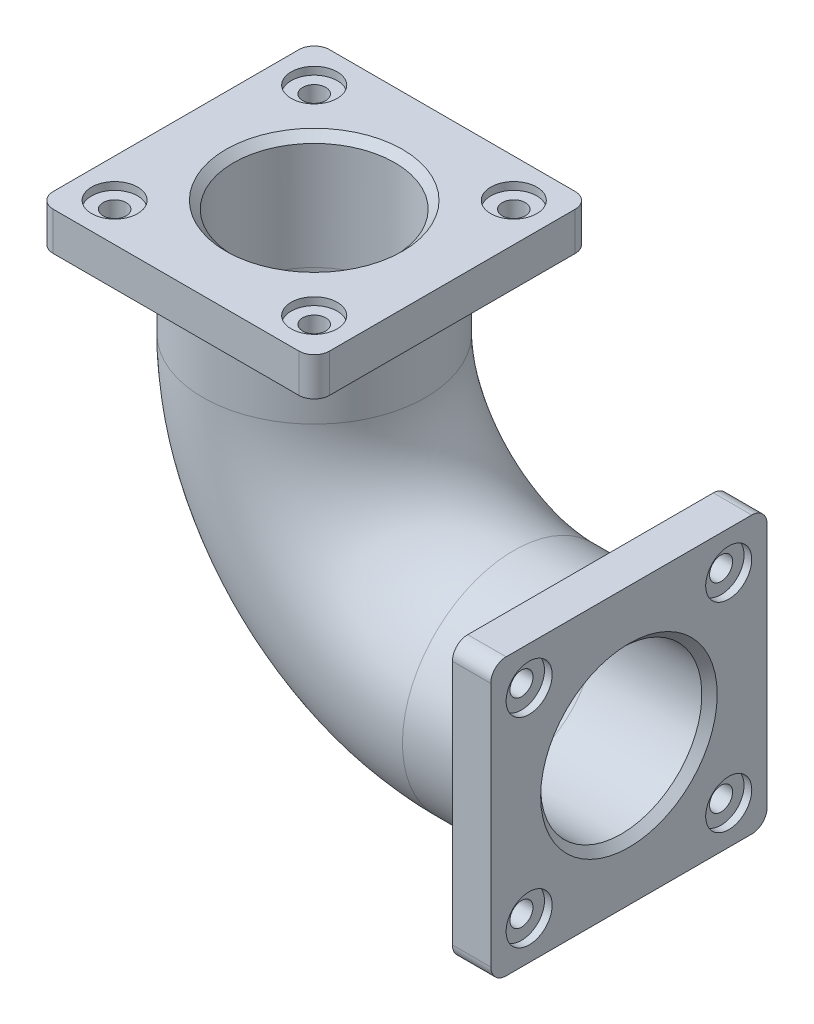
SolidWorks part; units mm, degrees
ref_plane "Front Plane" through (0, 0, 0) normal (0, 0, 1) x (1, 0, 0)
ref_plane "Top Plane" through (0, 0, 0) normal (0, 1, 0) x (1, 0, 0)
ref_plane "Right Plane" through (0, 0, 0) normal (1, 0, 0) x (0, 0, -1)
sketch "Sketch1" plane through (0, 0, 0) normal (0, 0, 1) x (1, 0, 0)
  line L0 (0, 0) -> (-150, 0)
  line L1 (-410, 260) -> (-410, 410)
  arc A0 (-150, 0) -> (-410, 260) centre (-150, 260) cw
  dimension "D3" = 260
  dimension "D1" = 150
  dimension "D2" = 150
sketch "Sketch2" plane through (0, 0, 0) normal (1, 0, 0) x (0, 0, -1)
  circle A0 centre (0, 0) radius 145
  dimension "D1" = 290
sweep "Sweep-Thin1" add profiles "Sketch2" path "Sketch1" parameters "D1"=40
sketch "Sketch3" plane through (0, 0, 0) normal (1, 0, 0) x (0, 0, -1)
  line L1 (-180, 180) -> (180, 180)
  line L2 (-180, 180) -> (-180, -180)
  line L3 (-180, -180) -> (180, -180)
  line L4 (180, 180) -> (180, -180)
  line L5 (-180, 180) -> (180, -180) construction
  line L6 (-180, -180) -> (180, 180) construction
  point P0 (0, 0)
  circle M5 centre (0, 0) radius 105
  circle M6 centre (0, 0) radius 145
  dimension "D1" = 360
  dimension "D2" = 360
extrude "Boss-Extrude1" add sketch "Sketch3" against normal blind 50 contours M5 | M6 M5 | L2 L1 L4 L3 region at (0, 0, 0) region at (0, 0, 140.8988)
fillet "Fillet1" radius 20 4 edges at (-25, -180, -180) (-25, -180, 180) (-25, 180, -180) (-25, 180, 180)
sketch "Sketch4" plane through (0, 410, 0) normal (0, 1, 0) x (1, 0, 0)
  line L1 (-590, 180) -> (-230, 180)
  line L2 (-590, 180) -> (-590, -180)
  line L3 (-590, -180) -> (-230, -180)
  line L4 (-230, 180) -> (-230, -180)
  line L5 (-590, 180) -> (-230, -180) construction
  line L6 (-590, -180) -> (-230, 180) construction
  point P0 (-410, 0)
  circle M6 centre (-410, 0) radius 145
  dimension "D1" = 360
  dimension "D2" = 360
extrude "Boss-Extrude2" add sketch "Sketch4" against normal blind 50 contours L4 L1 L2 L3 M6 region at (-410, 410, -174.9088)
fillet "Fillet2" radius 20 4 edges at (-590, 385, 180) (-230, 385, 180) (-230, 385, -180) (-590, 385, -180)
sketch "Sketch5" plane through (0, 0, 0) normal (1, 0, 0) x (0, 0, -1)
  line L1 (-130, 130) -> (130, 130) construction
  line L2 (-130, 130) -> (-130, -130) construction
  line L3 (-130, -130) -> (130, -130) construction
  line L4 (130, 130) -> (130, -130) construction
  line L5 (-130, 130) -> (130, -130) construction
  line L6 (-130, -130) -> (130, 130) construction
  circle A0 centre (-130, 130) radius 30
  circle A1 centre (130, 130) radius 30
  circle A2 centre (-130, -130) radius 30
  circle A3 centre (130, -130) radius 30
  point P0 (0, 0)
  dimension "D1" = 60
  dimension "D2" = 260
  dimension "D3" = 260
extrude "Cut-Extrude1" cut sketch "Sketch5" against normal blind 10
sketch "Sketch6" plane through (-10, 0, 0) normal (1, 0, 0) x (0, 0, -1)
  line L0 (0, 180) -> (0, -180) construction
  line L1 (-160, 180) -> (160, 180) construction
  line L2 (-160, -180) -> (160, -180) construction
  line L3 (-180, 0) -> (180, 0) construction
  line L4 (-180, 160) -> (-180, -160) construction
  line L5 (180, 160) -> (180, -160) construction
  circle A0 centre (-130, 130) radius 15
  circle A2 centre (130, 130) radius 15
  circle A3 centre (130, -130) radius 15
  circle A4 centre (-130, -130) radius 15
  dimension "D1" = 30
extrude "Cut-Extrude2" cut sketch "Sketch6" against normal up to next
sketch "Sketch7" plane through (0, 410, 0) normal (0, 1, 0) x (1, 0, 0)
  line L0 (-410, 130) -> (-410, -130) construction
  line L1 (-540, 130) -> (-280, 130) construction
  line L2 (-540, 130) -> (-540, -130) construction
  line L3 (-540, -130) -> (-280, -130) construction
  line L4 (-280, 130) -> (-280, -130) construction
  line L5 (-540, 130) -> (-280, -130) construction
  line L6 (-540, -130) -> (-280, 130) construction
  line L7 (-540, 0) -> (-280, 0) construction
  circle A0 centre (-540, 130) radius 30
  circle A1 centre (-280, 130) radius 30
  circle A2 centre (-280, -130) radius 30
  circle A3 centre (-540, -130) radius 30
  point P0 (-410, 0)
  dimension "D3" = 60
  dimension "D1" = 260
  dimension "D2" = 260
extrude "Cut-Extrude3" cut sketch "Sketch7" against normal blind 10 contours L1 A0 L2 | A1 L1 L4 | L3 A2 L4 | A3 L3 L2 region at (-540, 410, -130) region at (-280, 410, -130) region at (-280, 410, 130) region at (-540, 410, 130)
sketch "Sketch8" plane through (0, 400, 0) normal (0, 1, 0) x (1, 0, 0)
  circle A0 centre (-540, 130) radius 15
  dimension "D1" = 30
extrude "Cut-Extrude4" cut sketch "Sketch8" against normal up to next
pattern_circular "CirPattern1" count 4 over 360 about axis through (-410, 260, 0) along (0, 1, 0) of "Cut-Extrude3", "Cut-Extrude4" reverse direction yes
chamfer "Chamfer1" distance 10 angle 45 1 edges at (0, 0, -105) tangent propagation no
chamfer "Chamfer2" distance 10 angle 45 1 edges at (-305, 410, 0)
